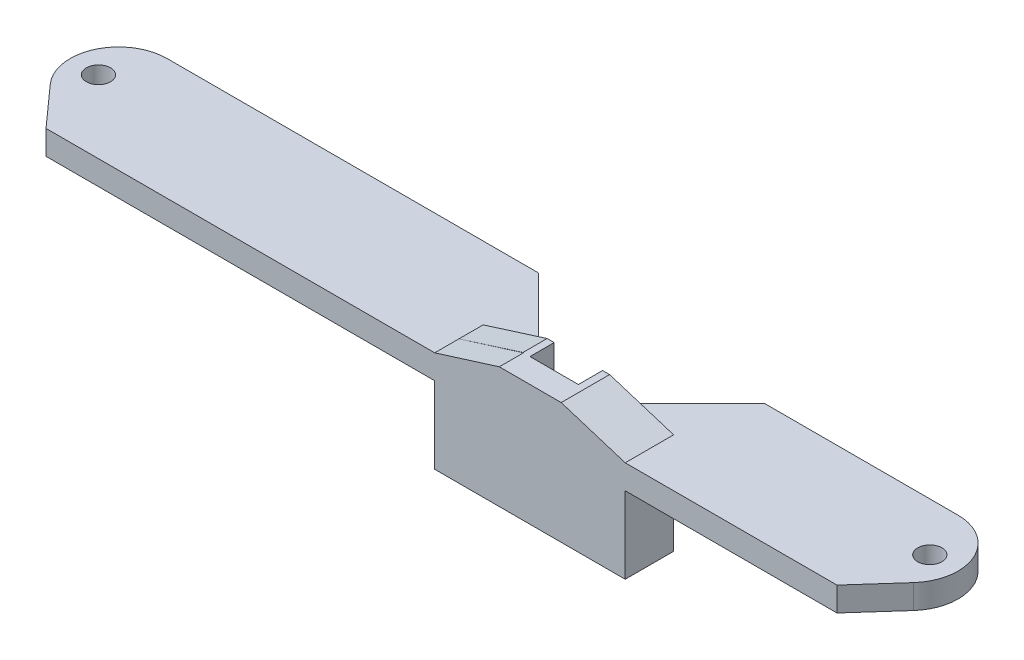
SolidWorks part; units mm, degrees
ref_plane "Front Plane" through (0, 0, 0) normal (0, 0, 1) x (1, 0, 0)
ref_plane "Top Plane" through (0, 0, 0) normal (0, 1, 0) x (1, 0, 0)
ref_plane "Right Plane" through (0, 0, 0) normal (1, 0, 0) x (0, 0, -1)
sketch "Sketch1" plane through (0, 0, 0) normal (0, 1, 0) x (1, 0, 0)
  line L0 (-49, 0) -> (49, 0) construction
  line L1 (-49, 6) -> (49, 6)
  line L2 (-49, -6) -> (49, -6)
  line L3 (-55, 0) -> (-55, -11)
  line L4 (-55, -11) -> (55, -11)
  line L5 (55, -11) -> (55, 0)
  arc A0 (-49, 6) -> (-49, -6) centre (-49, 0) ccw
  arc A1 (49, -6) -> (49, 6) centre (49, 0) ccw
  circle A2 centre (-51.5, 0) radius 1.5
  circle A3 centre (51.5, 0) radius 1.5
  point P2 (0, 0)
  point P12 (-55, 0)
  point P13 (55, 0)
  dimension "D3" = 3
  dimension "D4" = 3.5
  dimension "D1" = 110
  dimension "D2" = 12
  dimension "D5" = 3.5
  dimension "D6" = 5
extrude "Boss-Extrude1" add sketch "Sketch1" along normal blind 3 contours L2 A1 L1 A0 | A2 | A3
sketch "Sketch2" plane through (0, 3, 0) normal (0, 1, 0) x (1, 0, 0)
  line L0 (-9, 6) -> (0, -3)
  line L1 (-49, 6) -> (49, 6) construction
  line L2 (0, -3) -> (22, -3)
  line L3 (22, -3) -> (31, 6)
  line L4 (31, 6) -> (-9, 6)
  dimension "D1" = 135
  dimension "D2" = 135
  dimension "D3" = 40
  dimension "D4" = 22
extrude "Cut-Extrude1" cut sketch "Sketch2" against normal blind 10
sketch "Sketch8" plane through (0, 0, 6) normal (0, 0, 1) x (1, 0, 0)
  line L0 (10.9601, -11) -> (10.9601, 9.5817) construction
  line L1 (-49, 0) -> (49, 0) construction
  line L2 (7.9601, 3) -> (13.9601, 3)
  line L3 (7.9601, 3) -> (7.9601, 0)
  line L4 (7.9601, 0) -> (13.9601, 0)
  line L5 (13.9601, 3) -> (13.9601, 0)
  line L6 (7.9601, 3) -> (13.9601, 0) construction
  line L7 (7.9601, 0) -> (13.9601, 3) construction
  line L8 (-49, 3) -> (49, 3) construction
  point P1 (10.9601, 1.5)
  dimension "D1" = 6
extrude "Cut-Extrude3" cut sketch "Sketch8" along normal blind 4 from surface at -3 contours L3 L2 L5 L4 starting at face at (11, 1.5, 3)
sketch "Sketch9" plane through (0, 3, 0) normal (0, 1, 0) x (1, 0, 0)
  line L0 (13.9601, -6) -> (13.9601, -3) construction
  line L2 (7.9601, -6) -> (7.9601, -3) construction
  line L3 (13.9601, -6) -> (13.9601, -3)
  line L4 (7.9601, -6) -> (13.9601, -6)
  line L5 (7.9601, -6) -> (7.9601, -3)
  line L6 (14.7601, -6.8) -> (14.7601, -3)
  line L7 (7.1601, -6.8) -> (14.7601, -6.8)
  line L8 (7.1601, -6.8) -> (7.1601, -3)
  line L9 (7.1601, -3) -> (7.9601, -3)
  line L10 (13.9601, -3) -> (14.7601, -3)
  dimension "D1" = 0.8
extrude "Boss-Extrude4" add sketch "Sketch9" against normal blind 15 from offset 2.5 contours L10 L6 L7 L8 L9 L5 L4 L3
sketch "Sketch10" plane through (0, 0, 0) normal (0, 1, 0) x (1, 0, 0)
  line L0 (-9, 6) -> (-3, 6)
  line L1 (-3, 6) -> (6, -3)
  line L3 (16, -3) -> (25, 6)
  line L5 (25, 6) -> (31, 6)
  line L6 (31, 6) -> (22, -3)
  line L7 (22, -3) -> (16, -3)
  line L8 (-9, 6) -> (0, -3) construction
  line L9 (-9, 6) -> (0, -3)
  line L10 (0, -3) -> (6, -3)
  line L11 (0, -3) -> (7.1601, -3) construction
  dimension "D1" = 6
  dimension "D2" = 6
extrude "Boss-Extrude5" add sketch "Sketch10" along normal up to surface (3 mm away) contours L7 L6 L5 L3 | L10 L1 L0 L9 up to face at (30.82, 3, 1)
sketch "Sketch11" plane through (0, 3, 0) normal (0, 1, 0) x (1, 0, 0)
  line L0 (-0.8399, -3) -> (-0.8399, -6)
  line L1 (-49, -6) -> (7.1601, -6) construction
  line L2 (-0.8399, -6) -> (7.1601, -6)
  line L3 (7.1601, -6) -> (7.1601, -3)
  line L4 (7.1601, -3) -> (-0.8399, -3)
  line L5 (14.7601, -3) -> (22.7601, -3)
  line L6 (22.7601, -3) -> (22.7601, -6)
  line L7 (14.7601, -6) -> (49, -6) construction
  line L8 (22.7601, -6) -> (14.7601, -6)
  line L9 (14.7601, -6) -> (14.7601, -3)
  line M8 (16, -3) -> (14.7601, -3)
  line M9 (14.7601, -3) -> (14.7601, -6)
  line M10 (14.7601, -6) -> (49, -6)
  dimension "D1" = 8
  dimension "D2" = 8
extrude "Boss-Extrude6" add sketch "Sketch11" along direction (0, -1, 0) on the side against the normal blind 15 from offset 2.5 contours L3 L4 L0 L2 | L6 L5 M8 M9 M10
chamfer "Chamfer1" distance 2.5 angle 72.5 2 edges at (-0.8399, 5.5, 4.5) (22.7601, 5.5, 4.5)
sketch "Sketch12" plane through (0, 0, 6) normal (0, 0, -1) x (-1, 0, 0)
  line L0 (-7.9601, 5.5) -> (-7.9601, -9.5) construction
  line L1 (-13.9601, -9.5) -> (-7.9601, -9.5)
  line L2 (-13.9601, -9.5) -> (-13.9601, -9)
  line L3 (-13.9601, -9) -> (-7.9601, -9)
  line L4 (-7.9601, -9.5) -> (-7.9601, -9)
  dimension "D1" = 0.5
extrude "Boss-Extrude7" add sketch "Sketch12" along normal up to surface (3 mm away) up to face at (17.8789, -0.25, 3)
sketch "Sketch13" plane through (0, 0, 0) normal (0, 0, 1) x (1, 0, 0)
  line L5 (14.7601, 5.5) -> (7.1601, 5.5) construction
  line L7 (7.1601, -9.5) -> (14.7601, -9.5) construction
  line L18 (7.1601, 5.5) -> (-0.8399, 3)
  line L19 (-0.8399, 3) -> (-49, 3)
  line L21 (-49, 0) -> (-0.8399, 0)
  line L22 (-0.8399, 0) -> (-0.8399, -9.5)
  line L23 (-0.8399, -9.5) -> (7.1601, -9.5)
  line L28 (49, 3) -> (22.7601, 3) construction
  line L29 (22.7601, 3) -> (14.8311, 5.5) construction
  line L30 (14.8311, 5.5) -> (14.7601, 5.5) construction
  line L32 (14.7601, -9.5) -> (22.7601, -9.5) construction
  line L33 (22.7601, -9.5) -> (22.7601, 0) construction
  line L34 (22.7601, 0) -> (49, 0) construction
  line L39 (14.7601, 5.5) -> (7.1601, 5.5)
  line L40 (-49, 3) -> (-49, 0)
  line L41 (7.1601, -9.5) -> (14.7601, -9.5)
  line L42 (49, 3) -> (49, 0)
  line L46 (49, 3) -> (22.7601, 3)
  line L47 (22.7601, 3) -> (14.8311, 5.5)
  line L48 (14.8311, 5.5) -> (14.7601, 5.5)
  line L50 (14.7601, -9.5) -> (22.7601, -9.5)
  line L51 (22.7601, -9.5) -> (22.7601, 0)
  line L52 (22.7601, 0) -> (49, 0)
  point P0 (-0.8399, 0)
  point P9 (-0.8399, 3)
  point P10 (0, 0)
  point P12 (0, 0)
  point P14 (0, 0)
  point P17 (7.1601, 5.602)
extrude "Boss-Extrude8" add sketch "Sketch13" along normal blind 3 from surface at 6 starting at face at (26.3289, -0.25, 6)
sketch "Sketch14" plane through (0, 3, 0) normal (0, 1, 0) x (1, 0, 0)
  line L0 (-49, -9) -> (-53.4721, -4)
  line L1 (-49, -9) -> (-49, -6)
  line L2 (49, -9) -> (53.4721, -4)
  line L3 (0, -20.4814) -> (0, 7.0241) construction
  line L4 (49, -9) -> (49, -6)
  arc A0 (-49, 6) -> (-49, -6) centre (-49, 0) ccw construction
  arc A1 (-53.4721, -4) -> (-49, -6) centre (-49, 0) ccw
  arc A2 (53.4721, -4) -> (49, -6) centre (49, 0) cw
  point P13 (-49, -6.8)
  point P14 (-49, -9)
  point P16 (49, -9)
extrude "Boss-Extrude9" add sketch "Sketch14" against normal up to surface (3 mm away) up to face at (51.5, 0, 1.5)
